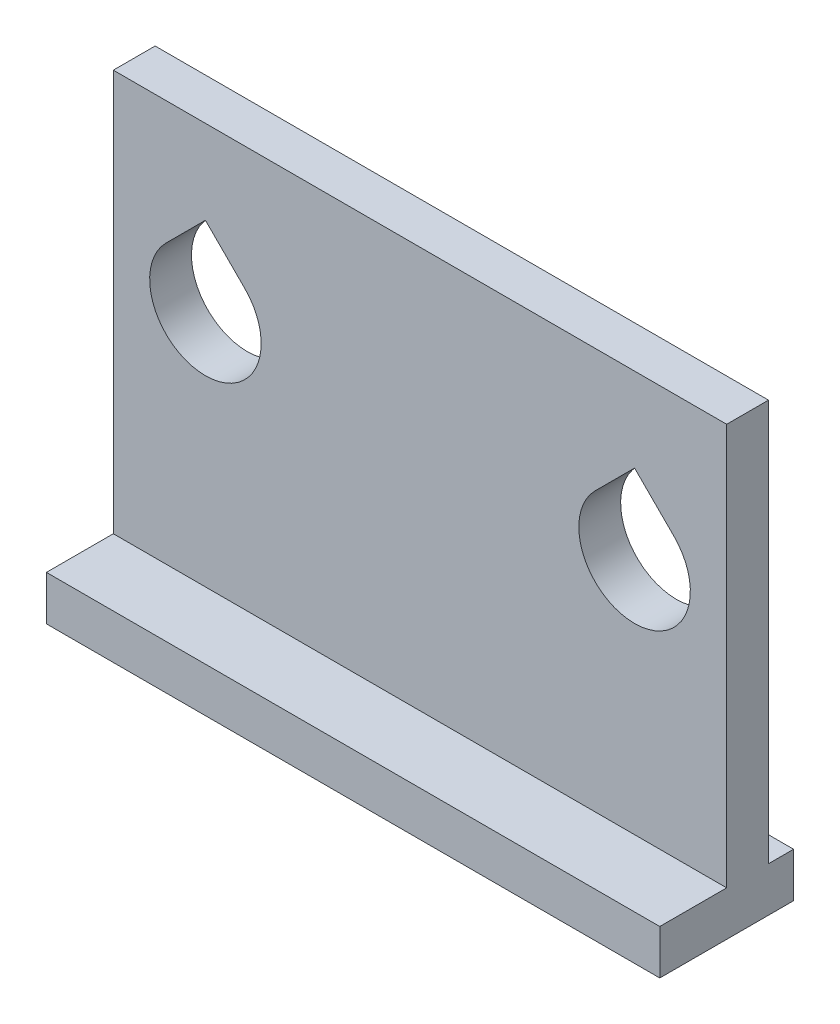
SolidWorks part; units mm, degrees
ref_plane "Front Plane" through (0, 0, 0) normal (0, 0, 1) x (1, 0, 0)
ref_plane "Top Plane" through (0, 0, 0) normal (0, 1, 0) x (1, 0, 0)
ref_plane "Right Plane" through (0, 0, 0) normal (1, 0, 0) x (0, 0, -1)
sketch "Sketch1" plane through (0, 0, 0) normal (0, 0, 1) x (1, 0, 0)
  line L0 (-38.481, 50.8) -> (38.481, 50.8) construction
  line L1 (-55, 0) -> (55, 0)
  line L2 (-55, 0) -> (-55, 80)
  line L3 (-55, 80) -> (55, 80)
  line L4 (55, 0) -> (55, 80)
  line L5 (38.481, 50.8) -> (0, 50.8)
  line L6 (0, 50.8) -> (0, 0) construction
  line L7 (-45.5521, 57.8711) -> (-38.481, 64.9421)
  line L8 (-38.481, 64.9421) -> (-31.4099, 57.8711)
  line L9 (31.4099, 57.8711) -> (38.481, 64.9421)
  line L10 (38.481, 64.9421) -> (45.5521, 57.8711)
  circle A0 centre (-38.481, 50.8) radius 10
  circle A1 centre (38.481, 50.8) radius 10
  point P4 (0, 0)
  dimension "D4" = 20
  dimension "D5" = 20
  dimension "D1" = 80
  dimension "D2" = 110
  dimension "D3" = 76.962
  dimension "D6" = 50.8
  dimension "D7" = 45
  dimension "D8" = 90
  dimension "D9" = 45
  dimension "D10" = 90
extrude "Boss-Extrude1" add sketch "Sketch1" along normal blind 7.5 contours L1 L4 L3 L2 A1 A0 region at (0, 39.0502, 0)
sketch "Sketch3" plane through (0, 0, 7.5) normal (0, 0, 1) x (1, 0, 0)
  line L0 (55, 0) -> (55, 80) construction
  line L1 (-55, 0) -> (55, 0)
  line L2 (-55, 0) -> (-55, 8)
  line L3 (-55, 8) -> (55, 8)
  line L4 (55, 0) -> (55, 8)
extrude "Boss-Extrude2" add sketch "Sketch3" along normal blind 12 and the other way blind 12
equation "\"shaftDiam\" = 20mm"
equation "\"keyW\" = 8mm"
equation "\"keyL\" = 10mm"
equation "\"clearance\" = .8mm"
equation "\"handleShaftLen\" = 60mm"
equation "\"panelH\" = 80mm"
equation "\"panelW\" = 110mm"
equation "\"D1@Sketch1\"=\"panelH\""
equation "\"D2@Sketch1\"=\"panelW\""
equation "\"D3@Sketch1\"=3.03in"
equation "\"D4@Sketch1\"=\"shaftDiam\""
equation "\"D5@Sketch1\"=\"shaftDiam\""
equation "\"D6@Sketch1\"=4in/2"
equation "\"D1@Boss-Extrude1\"=\"handleShaftLen\"/8"
equation "\"D1@Sketch3\"=\"panelH\"/10"
equation "\"D1@Boss-Extrude2\"=\"handleShaftLen\"/5"
equation "\"D2@Boss-Extrude2\"=\"handleShaftLen\"/5"
